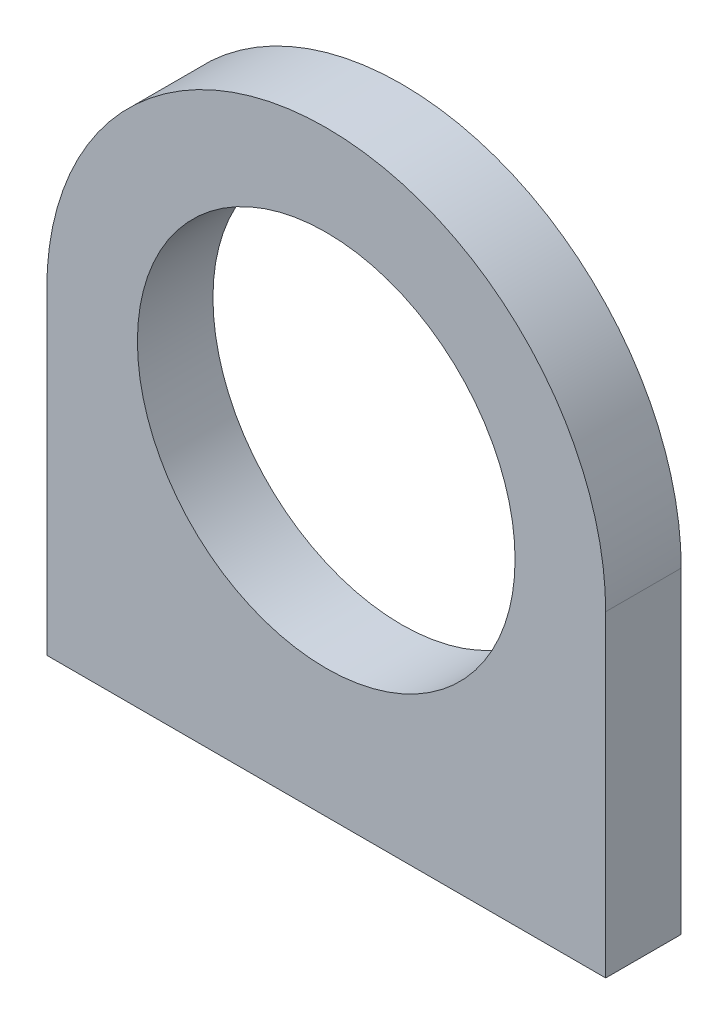
SolidWorks part; units mm, degrees
material "6061-T4 (SS)"
ref_plane "Front Plane" through (0, 0, 0) normal (0, 0, 1) x (1, 0, 0)
ref_plane "Top Plane" through (0, 0, 0) normal (0, 1, 0) x (1, 0, 0)
ref_plane "Right Plane" through (0, 0, 0) normal (1, 0, 0) x (0, 0, -1)
sketch "Sketch1" plane through (0, 0, 0) normal (0, 0, 1) x (1, 0, 0)
  line L0 (-18.5, 0) -> (-18.5, -21)
  line L1 (18.5, 0) -> (18.5, -21)
  line L2 (18.5, -21) -> (-18.5, -21)
  circle A0 centre (0, 0) radius 12.5
  circle A1 centre (0, 0) radius 18.5
  dimension "D1" = 25
  dimension "D2" = 37
  dimension "D3" = 21
extrude "Boss-Extrude1" add sketch "Sketch1" along normal blind 2.5 and the other way blind 2.5 contours A1 L0 L2 L1 | A1 A0 region at (0, -18.9254, 0) region at (0, 17.9767, 0)
sketch "Sketch2" plane through (0, -21, 0) normal (0, -1, 0) x (1, 0, 0)
  line L0 (0, -2.5) -> (0, 2.5)
  line L1 (18.5, -2.5) -> (-18.5, -2.5) construction
  line L2 (18.5, 2.5) -> (-18.5, 2.5) construction
  line L3 (0, 2.5) -> (0, 0)
  line L4 (0, 0) -> (-18.5, 0)
  line L5 (-18.5, 2.5) -> (-18.5, -2.5) construction
  circle A0 centre (-18.5, 0) radius 2.5
  circle A1 centre (-16, 0) radius 1.5
  point P11 (-16, 0)
  dimension "D1" = 5
  dimension "D2" = 3
extrude "Cut-Extrude1" cut sketch "Sketch2" against normal blind 10 contours A1
mirror "Mirror1" about plane through (0, 0, 0) normal (1, 0, 0) of "Cut-Extrude1"
